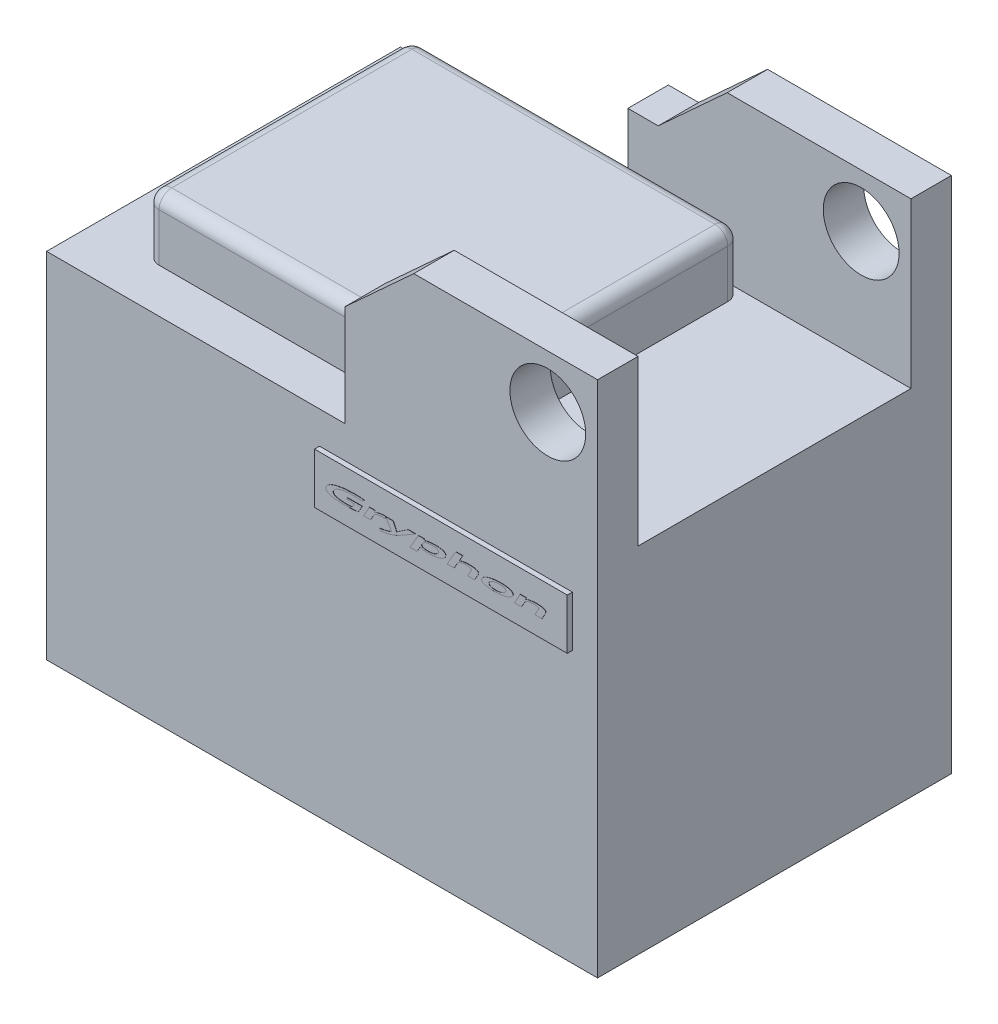
SolidWorks part; units mm, degrees
material "1060 Alloy"
ref_plane "Front Plane" through (0, 0, 0) normal (0, 0, 1) x (1, 0, 0)
ref_plane "Top Plane" through (0, 0, 0) normal (0, 1, 0) x (1, 0, 0)
ref_plane "Right Plane" through (0, 0, 0) normal (1, 0, 0) x (0, 0, -1)
sketch "Sketch2" plane through (0, 0, 0) normal (0, 1, 0) x (1, 0, 0)
  line L1 (-109, -70) -> (109, -70)
  line L2 (-109, -70) -> (-109, 70)
  line L3 (-109, 70) -> (109, 70)
  line L4 (109, -70) -> (109, 70)
  line L5 (-109, -70) -> (109, 70) construction
  line L6 (-109, 70) -> (109, -70) construction
  point P0 (0, 0)
  dimension "D1" = 218
  dimension "D2" = 140
extrude "Boss-Extrude1" add sketch "Sketch2" along normal blind 140
sketch "Sketch3" plane through (0, 140, 0) normal (0, 1, 0) x (1, 0, 0)
  line L1 (-87, -52.5) -> (43, -52.5)
  line L2 (-87, -52.5) -> (-87, 52.5)
  line L3 (-87, 52.5) -> (43, 52.5)
  line L4 (43, -52.5) -> (43, 52.5)
  line L5 (-87, -52.5) -> (43, 52.5) construction
  line L6 (-87, 52.5) -> (43, -52.5) construction
  line L8 (-133.3218, 0) -> (140.3321, 0) construction
  line L9 (-109, 70) -> (-109, -70) construction
  point P0 (-22, 0)
  dimension "D1" = 130
  dimension "D2" = 105
  dimension "D3" = 22
extrude "Boss-Extrude2" add sketch "Sketch3" along normal blind 24
fillet "Fillet1" radius 5 4 edges at (-22, 164, -52.5) (43, 164, 0) (-22, 164, 52.5) (-87, 164, 0)
fillet "Fillet2" radius 5 8 edges at (-85.5355, 162.5355, -51.0355) (41.5355, 162.5355, -51.0355) (41.5355, 162.5355, 51.0355) (-85.5355, 162.5355, 51.0355) (-87, 149.5, -52.5) (43, 149.5, -52.5) (43, 149.5, 52.5) (-87, 149.5, 52.5)
sketch "Sketch4" plane through (0, 0, 70) normal (0, 0, 1) x (1, 0, 0)
  line L0 (109, 140) -> (109, 205)
  line L1 (109, 205) -> (36.2764, 205)
  line L2 (36.2764, 205) -> (9, 180)
  line L3 (9, 180) -> (9, 140)
  line L4 (-109, 140) -> (109, 140) construction
  line L5 (9, 140) -> (109, 140)
  dimension "D1" = 65
  dimension "D2" = 100
  dimension "D3" = 40
  dimension "D4" = 37
  dimension "D5" = 72.7236
extrude "Boss-Extrude3" add sketch "Sketch4" against normal blind 16
sketch "Sketch5" plane through (0, 0, 70) normal (0, 0, 1) x (1, 0, 0)
  line L0 (109, 205) -> (36.2764, 205) construction
  line L1 (109, 205) -> (109, 0) construction
  circle A0 centre (89.3, 184) radius 15
  dimension "D1" = 30
  dimension "D2" = 21
  dimension "D3" = 19.7
extrude "Cut-Extrude1" cut sketch "Sketch5" against normal blind 16
mirror "Mirror1" about plane through (0, 0, 0) normal (0, 0, 1) of "Cut-Extrude1", "Boss-Extrude3"
sketch "Sketch6" plane through (0, 0, -70) normal (0, 0, -1) x (-1, 0, 0)
  line L1 (-9, 140) -> (3, 140)
  line L2 (-9, 140) -> (-9, 180)
  line L3 (-9, 180) -> (3, 180)
  line L4 (3, 140) -> (3, 180)
  dimension "D1" = 40
  dimension "D2" = 12
extrude "Boss-Extrude4" add sketch "Sketch6" against normal blind 16
sketch "Sketch7" plane through (0, 0, 70) normal (0, 0, 1) x (1, 0, 0)
  line L0 (109, 205) -> (109, 0) construction
  line L1 (99, 127.2378) -> (-1, 127.2378)
  line L2 (99, 127.2378) -> (99, 107.2378)
  line L3 (99, 107.2378) -> (-1, 107.2378)
  line L4 (-1, 127.2378) -> (-1, 107.2378)
  dimension "D1" = 100
  dimension "D2" = 20
  dimension "D3" = 10
extrude "Boss-Extrude5" add sketch "Sketch7" along normal blind 2
sketch "Sketch8" plane through (0, 0, 72) normal (0, 0, 1) x (1, 0, 0)
  line L0 (1.2315, 114.2044) -> (96.7257, 114.2044) construction
  text T0 "<b>Gryphon</b>" font "Kozuka Gothic Pr6N M" height in points 18
extrude "Boss-Extrude6" add sketch "Sketch8" along normal blind 0.1
sketch "Sketch9" plane through (0, 0, 0) normal (0, -1, 0) x (1, 0, 0)
  line L0 (109, 70) -> (109, -70) construction
  circle A0 centre (32, 0) radius 30
  dimension "D1" = 60
  dimension "D2" = 77
extrude "Cut-Extrude2" cut sketch "Sketch9" against normal blind 1
